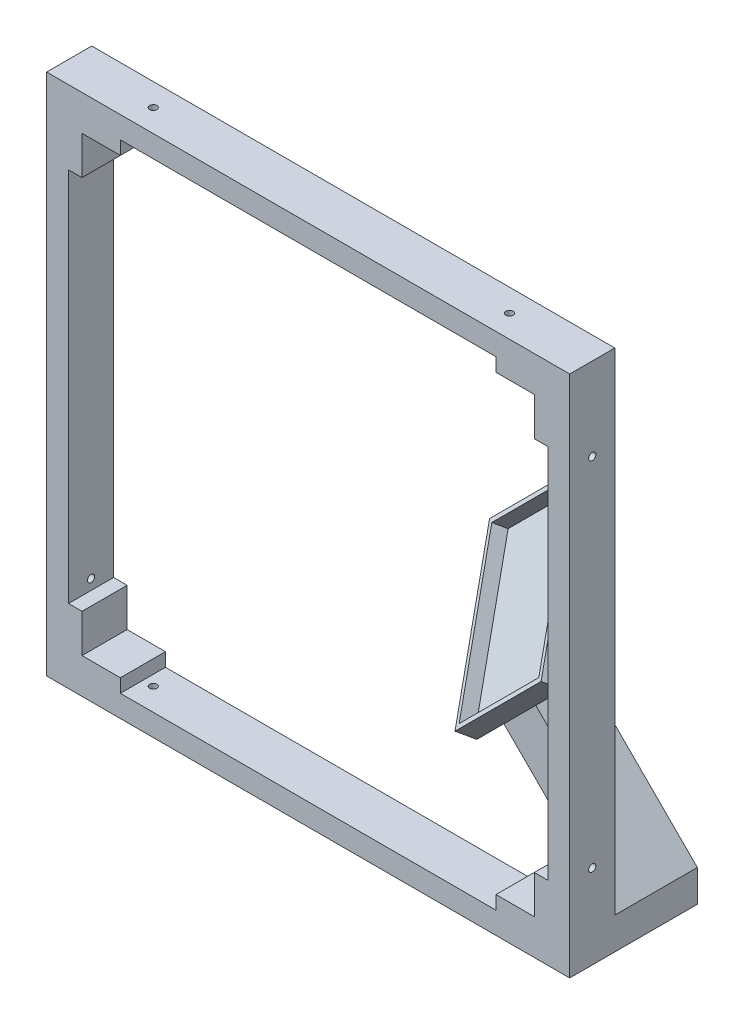
SolidWorks part; units mm, degrees
material "Nylon 101"
ref_plane "Front Plane" through (0, 0, 0) normal (0, 0, 1) x (1, 0, 0)
ref_plane "Top Plane" through (0, 0, 0) normal (0, 1, 0) x (1, 0, 0)
ref_plane "Right Plane" through (0, 0, 0) normal (1, 0, 0) x (0, 0, -1)
sketch "Sketch1" plane through (0, 0, 0) normal (0, 0, 1) x (1, 0, 0)
  line L13 (50.0019, -50.0019) -> (58, -58) construction
  line L14 (53, -41.5) -> (50.0019, -41.5)
  line L17 (41.5, -53) -> (41.5, -50.0019)
  line L18 (50.0019, -44.9586) -> (53, -44.9586)
  line L20 (53, -44.9586) -> (53, -53)
  line L23 (53, -53) -> (44.9586, -53)
  line L24 (44.9586, -53) -> (44.9586, -50.0019)
  line L25 (50.0019, -41.5) -> (50.0019, -50.0019)
  line L27 (50.0019, -50.0019) -> (41.5, -50.0019)
  line L35 (-41.5, 53) -> (41.5, 53)
  line L37 (50.0019, -50.0019) -> (50.0019, -41.5)
  line L38 (41.5, -50.0019) -> (50.0019, -50.0019)
  line L39 (53, -44.9586) -> (50.0019, -44.9586)
  line L40 (53, -53) -> (53, -44.9586)
  line L42 (44.9586, -53) -> (53, -53)
  line L43 (44.9586, -50.0019) -> (44.9586, -53)
  line L44 (53, -41.5) -> (50.0019, -41.5)
  line L45 (41.5, -53) -> (41.5, -50.0019)
  line L47 (53, -41.5) -> (53, 41.5)
  line L50 (41.5, -53) -> (-41.5, -53)
  line L52 (-41.5, -53) -> (-41.5, -50.0019)
  line L53 (-53, -41.5) -> (-50.0019, -41.5)
  line L54 (-44.96, -50.0019) -> (-44.96, -53)
  line L55 (-44.96, -53) -> (-53, -53)
  line L57 (-53, -53) -> (-53, -44.96)
  line L58 (-53, -44.96) -> (-50.0019, -44.96)
  line L59 (-41.5, -50.0019) -> (-50.0019, -50.0019)
  line L60 (-50.0019, -50.0019) -> (-50.0019, -41.5)
  line L61 (-53, -41.5) -> (-53, 41.5)
  line L63 (58, 58) -> (58, -58)
  line L65 (-50.0019, -50.0019) -> (-41.5, -50.0019)
  line L66 (-50.0019, -41.5) -> (-50.0019, -50.0019)
  line L67 (-44.96, -53) -> (-44.96, -50.0019)
  line L68 (-53, -53) -> (-44.96, -53)
  line L70 (-53, -44.96) -> (-53, -53)
  line L71 (-50.0019, -44.96) -> (-53, -44.96)
  line L72 (-41.5, -53) -> (-41.5, -50.0019)
  line L73 (-53, -41.5) -> (-50.0019, -41.5)
  line L75 (58, -58) -> (-58, -58)
  line L77 (-50.0019, -50.0019) -> (-58, -58) construction
  line L79 (-58, -58) -> (-58, 58)
  line L81 (-53, 41.5) -> (-50.0019, 41.5)
  line L82 (-41.5, 53) -> (-41.5, 50.0019)
  line L83 (-50.0019, 44.96) -> (-53, 44.96)
  line L84 (-53, 44.96) -> (-53, 53)
  line L86 (-53, 53) -> (-44.96, 53)
  line L87 (-44.96, 53) -> (-44.96, 50.0019)
  line L88 (-50.0019, 41.5) -> (-50.0019, 50.0019)
  line L89 (-50.0019, 50.0019) -> (-41.5, 50.0019)
  line L90 (-58, 58) -> (58, 58)
  line L94 (-50.0019, 50.0019) -> (-50.0019, 41.5)
  line L95 (-41.5, 50.0019) -> (-50.0019, 50.0019)
  line L96 (-53, 44.96) -> (-50.0019, 44.96)
  line L97 (-53, 53) -> (-53, 44.96)
  line L99 (-44.96, 53) -> (-53, 53)
  line L100 (-44.96, 50.0019) -> (-44.96, 53)
  line L101 (-53, 41.5) -> (-50.0019, 41.5)
  line L102 (-41.5, 53) -> (-41.5, 50.0019)
  line L106 (-50.0019, 50.0019) -> (-58, 58) construction
  line L110 (41.5, 53) -> (41.5, 50.0019)
  line L111 (53, 41.5) -> (50.0019, 41.5)
  line L112 (44.9586, 50.0019) -> (44.9586, 53)
  line L113 (44.9586, 53) -> (53, 53)
  line L115 (53, 53) -> (53, 44.96)
  line L116 (53, 44.96) -> (50.0019, 44.96)
  line L117 (41.5, 50.0019) -> (50.0019, 50.0019)
  line L118 (50.0019, 50.0019) -> (50.0019, 41.5)
  line L123 (50.0019, 50.0019) -> (41.5, 50.0019)
  line L124 (50.0019, 41.5) -> (50.0019, 50.0019)
  line L125 (44.9586, 53) -> (44.9586, 50.0019)
  line L126 (53, 53) -> (44.9586, 53)
  line L128 (53, 44.96) -> (53, 53)
  line L129 (50.0019, 44.96) -> (53, 44.96)
  line L130 (41.5, 53) -> (41.5, 50.0019)
  line L131 (53, 41.5) -> (50.0019, 41.5)
  line L135 (50.0019, 50.0019) -> (58, 58) construction
  point P2 (0, 58)
  point P4 (0, 53)
  point P6 (0, -53)
  point P7 (0, -58)
  point P10 (53, 0)
  point P11 (-53, 0)
  point P16 (-58, 0)
  point P17 (58, 0)
  dimension "D1" = 106
  dimension "D2" = 5
  dimension "D3" = 2.9981
extrude "base" add sketch "Sketch1" along normal mid plane 10 contours L20 L13 L14 L25 L18 | L13 L23 L24 L27 L17 | L13 L27 L24 L23 | L25 L13 L20 L18 | L117 L118 L116 L115 L113 L112 | L88 L89 L87 L86 L84 L83 | L59 L60 L58 L57 L55 L54 region at (51.5009, -45.0723, 0) region at (50.1156, 47.4809, 0) region at (-45.0737, -51.5009, 0) region at (-47.4809, 50.1156, 0) region at (56.3595, 0, 0)
ref_plane "Plane3" through (0, 0, 15) normal (0, 0, 1) x (1, 0, 0)
sketch "Sketch7" plane through (0, 0, 15) normal (0, 0, 1) x (1, 0, 0)
  line L0 (-41.65, 53.15) -> (41.65, 53.15)
  line L1 (41.65, 53.15) -> (41.65, 50.1519)
  line L2 (41.65, 50.1519) -> (50.1519, 50.1519)
  line L3 (50.1519, 50.1519) -> (50.1519, 41.65)
  line L4 (50.1519, 41.65) -> (53.15, 41.65)
  line L5 (53.15, 41.65) -> (53.15, -41.65)
  line L6 (53.15, -41.65) -> (50.1519, -41.65)
  line L7 (50.1519, -41.65) -> (50.1519, -50.1519)
  line L8 (50.1519, -50.1519) -> (41.65, -50.1519)
  line L9 (41.65, -50.1519) -> (41.65, -53.15)
  line L10 (41.65, -53.15) -> (-41.65, -53.15)
  line L11 (-41.65, -53.15) -> (-41.65, -50.1519)
  line L12 (-41.65, -50.1519) -> (-50.1519, -50.1519)
  line L13 (-50.1519, -50.1519) -> (-50.1519, -41.65)
  line L14 (-50.1519, -41.65) -> (-53.15, -41.65)
  line L15 (-53.15, -41.65) -> (-53.15, 41.65)
  line L16 (-53.15, 41.65) -> (-50.1519, 41.65)
  line L17 (-50.1519, 41.65) -> (-50.1519, 50.1519)
  line L18 (-50.1519, 50.1519) -> (-41.65, 50.1519)
  line L19 (-41.65, 50.1519) -> (-41.65, 53.15)
  line L21 (-41.5, 53) -> (41.5, 53) construction
  line L22 (-41.5, 53) -> (-41.5, 50.0019) construction
  line L23 (-50.0019, 50.0019) -> (-41.5, 50.0019) construction
  line L24 (-50.0019, 41.5) -> (-50.0019, 50.0019) construction
  line L25 (-53, 41.5) -> (-50.0019, 41.5) construction
  line L26 (-53, -41.5) -> (-53, 41.5) construction
  line L27 (-53, -41.5) -> (-50.0019, -41.5) construction
  line L28 (-50.0019, -50.0019) -> (-50.0019, -41.5) construction
  line L29 (-41.5, -50.0019) -> (-50.0019, -50.0019) construction
  line L30 (-41.5, -53) -> (-41.5, -50.0019) construction
  line L31 (41.5, -53) -> (-41.5, -53) construction
  line L32 (41.5, -53) -> (41.5, -50.0019) construction
  line L33 (50.0019, -41.5) -> (50.0019, -50.0019) construction
  line L34 (53, -41.5) -> (53, 41.5) construction
  line L35 (50.0019, 50.0019) -> (50.0019, 41.5) construction
  line L36 (53, 41.5) -> (50.0019, 41.5) construction
  line L37 (41.5, 50.0019) -> (50.0019, 50.0019) construction
  dimension "D1" = 0.15
  dimension "D2" = 0.15
  dimension "D3" = 0.15
  dimension "D4" = 0.15
  dimension "D5" = 0.15
  dimension "D6" = 0.15
  dimension "D7" = 0.15
  dimension "D8" = 0.15
  dimension "D9" = 0.15
  dimension "D10" = 0.15
  dimension "D11" = 0.15
  dimension "D12" = 0.15
  dimension "D13" = 0.15
  dimension "D14" = 0.15
  dimension "D15" = 0.15
  dimension "D16" = 0.15
  dimension "D17" = 0.15
ref_plane "arm plane" through (0, 0, 0) normal (0.7071, 0.7071, 0) x (0.7071, -0.7071, 0)
sketch "Sketch2" plane through (0, 0, 0) normal (0.7071, 0.7071, 0) x (0.7071, -0.7071, 0)
  line L4 (70.9255, 5) -> (82.0244, 5)
  line L6 (66.8216, 5) -> (8.1317, 5) construction
  line L8 (82.0244, 5) -> (82.0244, 23.31)
  line L9 (82.0244, 23.31) -> (31.0282, 23.31)
  line L12 (31.0282, 23.31) -> (42.3382, 12)
  line L13 (42.3382, 12) -> (70.9255, 12)
  line L14 (70.9255, 12) -> (70.9255, 5)
  point P2 (0, 0)
  point P9 (106.7839, -11.9879)
  point P10 (0, 0)
  dimension "D1" = 45
  dimension "D2" = 11.31
  dimension "D3" = 50.9962
  dimension "D4" = 7
extrude "arm" add sketch "Sketch2" along normal mid plane 10
sketch "Sketch3" plane through (0, 0, 0) normal (0, 0, 1) x (1, 0, 0)
  line L1 (61.5355, -54.4645) -> (54.4645, -61.5355) construction
  line L6 (58, 58) -> (58, -50.9289) construction
  line L7 (50.9289, -58) -> (-58, -58) construction
  line L8 (26.4021, -33.4731) -> (46.6163, -53.6874) construction
  line L9 (58, -50.9289) -> (61.5355, -54.4645) construction
  line L10 (54.818, -61.8891) -> (61.8891, -54.818)
  line L11 (61.8891, -54.818) -> (58, -50.9289)
  line L12 (58, -50.9289) -> (58, -58)
  line L13 (58, -58) -> (50.9289, -58)
  line L14 (50.9289, -58) -> (54.818, -61.8891)
  dimension "D1" = 0.5
extrude "Cut-Extrude1" cut sketch "Sketch3" against normal through all
ref_plane "Plane2" through (0, 0, -5) normal (0, 0, -1) x (-1, 0, 0)
sketch "Sketch5" plane through (0, 0, -5) normal (0, 0, -1) x (-1, 0, 0)
  line L0 (-46.6163, -53.6874) -> (-43.0808, -50.1519)
  line L7 (-50.1519, -43.0808) -> (-53.6874, -46.6163)
  line L8 (-53.6874, -46.6163) -> (-53.6874, -53.6874)
  line L9 (-50.0019, -50.0019) -> (-58, -58) construction
  line L10 (-53.6874, -53.6874) -> (-46.6163, -53.6874)
  line L12 (-53.6874, -46.6163) -> (-58, -50.9289) construction
  line L14 (-50.1519, -41.65) -> (-50.1519, -50.1519) construction
  line L15 (-50.1519, -50.1519) -> (-41.65, -50.1519) construction
  line L16 (-50.1519, -43.0808) -> (-50.1519, -50.1519)
  line L17 (-50.1519, -50.1519) -> (-43.0808, -50.1519)
  dimension "D1" = 5
  dimension "D2" = 10
extrude "Boss-Extrude4" add sketch "Sketch5" along normal up to surface (7 mm away) contours L8 L10 L0 L7 | L7 L8 L10 L0 L17 L16 region at (50.1519, -53.5374, -5) up to face at (40.0447, -40.0447, -12)
ref_plane "Mirror Plane" through (19.2114, -19.2114, -27.1691) normal (-0.5, 0.5, 0.7071) x (0.866, 0.2887, 0.4082)
sketch "Sketch9" plane through (19.2114, -19.2114, -27.1691) normal (-0.5, 0.5, 0.7071) x (0.866, 0.2887, 0.4082)
  line L0 (1.3628, -25.31) -> (23.4082, -9.7215)
  line L1 (-19.9992, 4.9004) -> (23.4082, -9.7215) construction
  line L2 (16.468, -14.629) -> (8.303, -20.4025) construction
  line L3 (1.3628, -25.31) -> (-19.9992, 4.9004)
  line L4 (-19.9992, 4.9004) -> (2.0462, 20.4889)
  line L5 (2.0462, 20.4889) -> (23.4082, -9.7215)
  line L6 (2.0462, 20.4889) -> (1.3628, -25.31) construction
  line L7 (1.8071, 19.095) -> (-18.6053, 4.6613)
  line L8 (-18.6053, 4.6613) -> (1.6019, -23.9161)
  line L9 (1.6019, -23.9161) -> (22.0144, -9.4824)
  line L10 (22.0144, -9.4824) -> (1.8071, 19.095)
  line L11 (1.6019, -23.9161) -> (1.8071, 19.095) construction
  line L12 (-18.6053, 4.6613) -> (22.0144, -9.4824) construction
  point P4 (12.3855, -17.5157)
  point P5 (12.3855, -17.5157)
  point P12 (1.7045, -2.4106)
  point P13 (1.7045, -2.4106)
  dimension "D1" = 27
  dimension "D2" = 37
  dimension "D3" = 1
  dimension "D4" = 1
extrude "Boss-Extrude5" add sketch "Sketch9" along normal blind 4
extrude "Boss-Extrude6" add sketch "Sketch9<2>" along normal blind 1 contours L9 L10 L7 L8 region at (20.6876, -20.6876, -25.0815)
sketch "Sketch9<2>" plane through (19.2114, -19.2114, -27.1691) normal (-0.5, 0.5, 0.7071) x (0.866, 0.2887, 0.4082) same geometry as "Sketch9"
extrude "clearance" cut sketch "Sketch7" against normal up to surface (20 mm away) up to face at (0, 0, -5)
sketch "Sketch10" plane through (0, 0, 0) normal (0, 1, 0) x (1, 0, 0)
  line L0 (41.65, 5) -> (41.65, -5) construction
  circle A0 centre (39.65, 0) radius 0.8
  circle A1 centre (-39.35, 0) radius 0.8
  point P4 (0, 0)
  point P5 (41.65, 0)
  point P10 (0, 0)
  point P11 (-96.7737, -6.4391)
  dimension "D1" = 1.6
  dimension "D2" = 2
  dimension "D3" = 79
hole_wizard "M2x0.4 Tapped Hole1" positions "Sketch11" profile "Sketch12" tap size "M2x0.4" standard "ANSI Metric" end condition through all
sketch "Sketch11" plane through (0, 0, 0) normal (0, 1, 0) x (1, 0, 0)
  point P0 (-39.35, 0)
  point P2 (39.65, 0)
  point P7 (0, 0)
  point P9 (-9.2955, -2.4142)
  point P10 (0, 0)
  point P11 (0, 0)
sketch "Sketch12" plane through (-39.35, 0, 0) normal (1, 0, 0) x (0, 0, -1)
  line L0 (0, 0) -> (0, 58)
  line L1 (0, 58) -> (0.8, 58)
  line L2 (0.8, 58) -> (0.8, 0)
  line L5 (0.8, 0) -> (0, 0)
  line L11 (0, -6.35) -> (0, 107.95) construction
  dimension "Thru Tap Drill Dia." = 1.6
  dimension "Thru Tap Drill Depth" = 58
cosmetic thread "Hole Thread1" parameters "D2"=2
cosmetic thread "Hole Thread2" parameters "D2"=2
mirror "Mirror1" about plane through (0, 0, 0) normal (0, 1, 0) of "M2x0.4 Tapped Hole1"
cosmetic thread "Hole Thread3" parameters "D2"=2
cosmetic thread "Hole Thread4" parameters "D2"=2
sketch "Sketch13" plane through (0, 0, 0) normal (1, 0, 0) x (0, 0, -1)
  line L2 (5, 41.65) -> (-5, 41.65) construction
  circle A0 centre (0, 39.65) radius 0.8
  circle A1 centre (0, -39.35) radius 0.8
  point P2 (0, 0)
  dimension "D1" = 1.6
  dimension "D3" = 79
  dimension "D2" = 2
hole_wizard "M2x0.4 Tapped Hole2" positions "Sketch14" profile "Sketch15" tap size "M2x0.4" standard "ANSI Metric" end condition through all
sketch "Sketch14" plane through (0, 0, 0) normal (1, 0, 0) x (0, 0, -1)
  point P0 (0, 39.65)
  point P3 (0, -39.35)
sketch "Sketch15" plane through (0, 39.65, 0) normal (0, 1, 0) x (0, 0, 1)
  line L0 (0, 0) -> (0, 58)
  line L1 (0, 58) -> (0.8, 58)
  line L2 (0.8, 58) -> (0.8, 0)
  line L5 (0.8, 0) -> (0, 0)
  line L11 (0, -6.35) -> (0, 107.95) construction
  dimension "Thru Tap Drill Dia." = 1.6
  dimension "Thru Tap Drill Depth" = 58
cosmetic thread "Hole Thread5" parameters "D2"=2
cosmetic thread "Hole Thread6" parameters "D2"=2
mirror "Mirror2" about plane through (0, 0, 0) normal (1, 0, 0) of "M2x0.4 Tapped Hole2"
cosmetic thread "Hole Thread7" parameters "D2"=2
cosmetic thread "Hole Thread8" parameters "D2"=2
